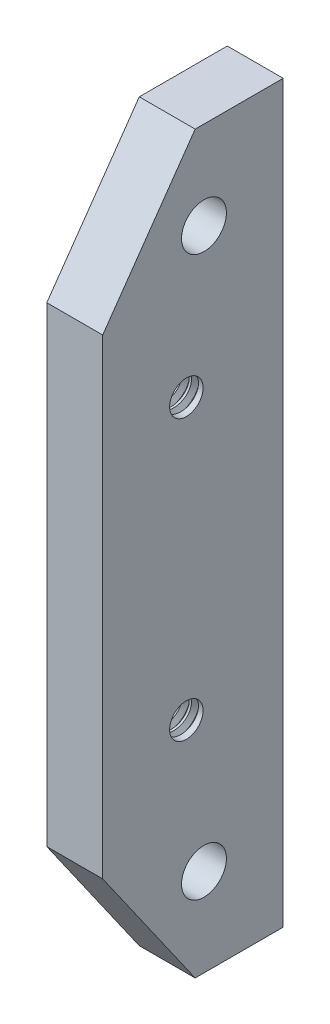
SolidWorks part; units mm, degrees
ref_plane "Front Plane" through (0, 0, 0) normal (0, 0, 1) x (1, 0, 0)
ref_plane "Top Plane" through (0, 0, 0) normal (0, 1, 0) x (1, 0, 0)
ref_plane "Right Plane" through (0, 0, 0) normal (1, 0, 0) x (0, 0, -1)
sketch "Sketch1" plane through (0, 0, 0) normal (1, 0, 0) x (0, 0, -1)
  line L0 (0, 0) -> (9, 0) construction
  line L1 (0, -31.75) -> (0, 31.75) construction
  line L2 (-12.4312, 25.4) -> (9, 25.4) construction
  line L3 (-12.4312, 25.4) -> (-12.4312, -25.4) construction
  line L4 (-12.4312, -25.4) -> (9, -25.4) construction
  line L5 (9, 25.4) -> (9, -25.4) construction
  line L6 (-2, -15.875) -> (-2, 15.875) construction
  line L8 (-11.5, 41.75) -> (9, 41.75)
  line L9 (-11.5, 41.75) -> (-11.5, -41.75)
  line L10 (-11.5, -41.75) -> (9, -41.75)
  line L11 (9, 41.75) -> (9, -41.75)
  circle A0 centre (0, 31.75) radius 2.55
  circle A1 centre (0, -31.75) radius 2.55
  circle A2 centre (-2, 15.875) radius 1.8986
  circle A3 centre (-2, -15.875) radius 1.8986
  point P6 (0, 0)
  point P16 (-2, 0)
  dimension "D1" = 5.1
  dimension "D2" = 5.1
  dimension "D12" = 3.7973
  dimension "D13" = 3.7973
  dimension "D3" = 63.5
  dimension "D4" = 50.8
  dimension "D5" = 21.4312
  dimension "D6" = 31.75
  dimension "D7" = 11
  dimension "D8" = 9
  dimension "D9" = 10
  dimension "D10" = 10
  dimension "D11" = 9.5
extrude "Boss-Extrude1" add sketch "Sketch1" along normal blind 3.175 and the other way blind 3.175
chamfer "Chamfer1" distance 15 angle 35 1 edges at (0, 41.75, 11.5) first distance on face at (0, 0, 11.5)
chamfer "Chamfer2" distance 15 angle 35 1 edges at (0, -41.75, 11.5) first distance on face at (0, -7.5, 11.5)
thread "Thread1" pitch 1.0583 method cut profile "Thread Profile1" start angle 0, offset 0, length 10, pitch 1.0583, diameter 3.7973
ref_plane "Plane1" through (3.175, 15.875, 3.8986) normal (0, -1, 0) x (0, 0, 1)
sketch "Thread Profile1" plane through (3.175, 15.875, 3.8986) normal (0, -1, 0) x (0, 0, 1)
  line L0 (0, 0) -> (0, 1.0583) construction
  line L1 (0, 0) -> (0.5728, 0.3307)
  line L2 (0.5728, 0.3307) -> (0.5728, 0.463)
  line L3 (0.5728, 0.463) -> (0, 0.7937)
  line L4 (0.5728, 0.3969) -> (0, 0.3969) construction
  line L11 (0, 0) -> (0, 0.7937)
  point P2 (0, 0)
  dimension "Pitch" = 1.0583
  dimension "Profile_Angle" = 60
  dimension "Profile_Land" = 0.1323
  dimension "Profile_Height" = 0.5728
thread "Thread2" pitch 1.0583 method cut profile "Thread Profile2" start angle 0, offset 0, length 10, pitch 1.0583, diameter 3.7973
ref_plane "Plane2" through (3.175, -15.875, 3.8986) normal (0, -1, 0) x (0, 0, 1)
sketch "Thread Profile2" plane through (3.175, -15.875, 3.8986) normal (0, -1, 0) x (0, 0, 1)
  line L0 (0, 0) -> (0, 1.0583) construction
  line L1 (0, 0) -> (0.5728, 0.3307)
  line L2 (0.5728, 0.3307) -> (0.5728, 0.463)
  line L3 (0.5728, 0.463) -> (0, 0.7937)
  line L4 (0.5728, 0.3969) -> (0, 0.3969) construction
  line L11 (0, 0) -> (0, 0.7937)
  point P2 (0, 0)
  dimension "Pitch" = 1.0583
  dimension "Profile_Angle" = 60
  dimension "Profile_Land" = 0.1323
  dimension "Profile_Height" = 0.5728
